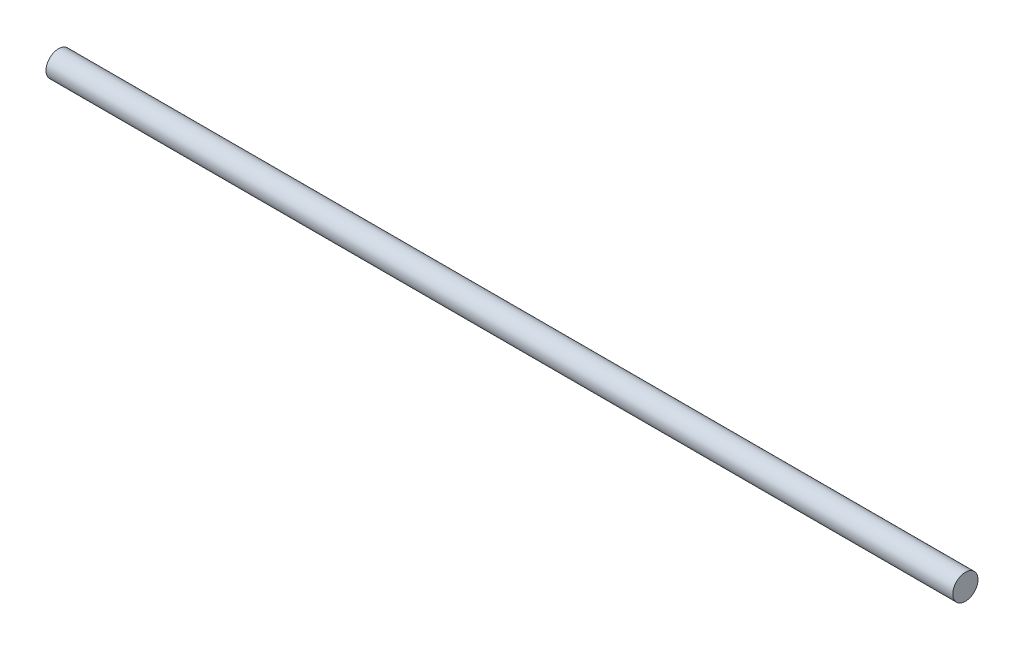
SolidWorks part; units mm, degrees
ref_plane "Front Plane" through (0, 0, 0) normal (0, 0, 1) x (1, 0, 0)
ref_plane "Top Plane" through (0, 0, 0) normal (0, 1, 0) x (1, 0, 0)
ref_plane "Right Plane" through (0, 0, 0) normal (1, 0, 0) x (0, 0, -1)
sketch "Sketch1" plane through (0, 0, 0) normal (1, 0, 0) x (0, 0, -1)
  circle A0 centre (0, 0) radius 6.35
  dimension "D1" = 12.7
extrude "Boss-Extrude1" add sketch "Sketch1" along normal blind 457.2
